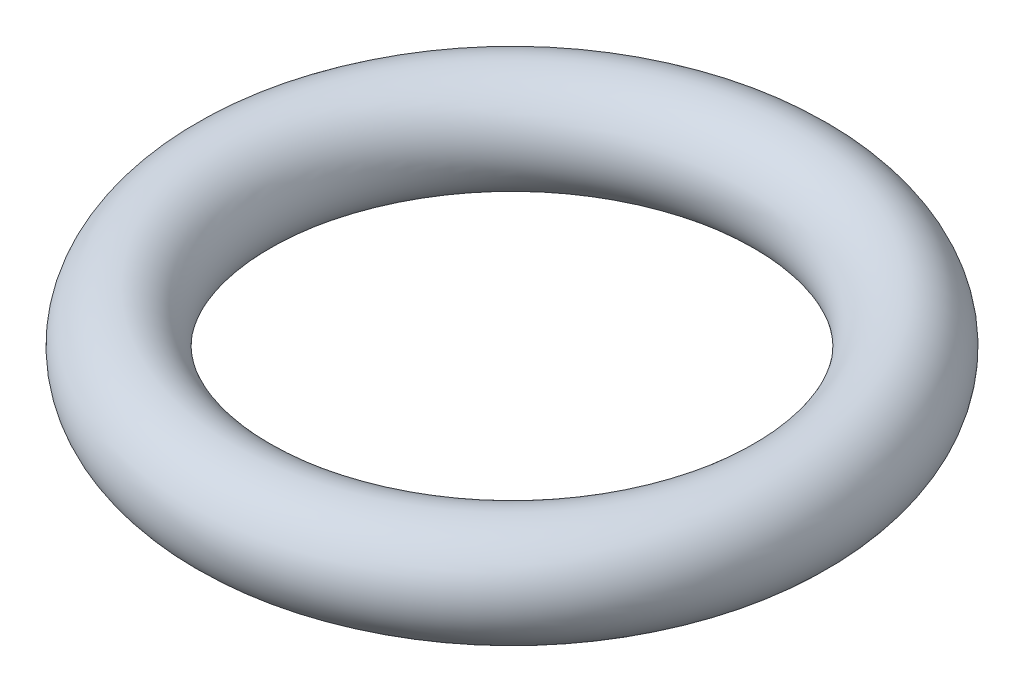
SolidWorks part; units mm, degrees
ref_plane "Front Plane" through (0, 0, 0) normal (0, 0, 1) x (1, 0, 0)
ref_plane "Top Plane" through (0, 0, 0) normal (0, 1, 0) x (1, 0, 0)
ref_plane "Right Plane" through (0, 0, 0) normal (1, 0, 0) x (0, 0, -1)
sketch "Sketch1" plane through (0, 0, 0) normal (0, 0, 1) x (1, 0, 0)
  line L0 (0, 0) -> (4.69, 0) construction
  line L1 (0, 0) -> (0, 8.2441) construction
  circle A0 centre (4.69, 0) radius 0.865
  dimension "D2" = 5.555
  dimension "D1" = 3.825
revolve "Revolve1" add sketch "Sketch1" angle 360 about L1
ref_axis "Axis1" through (0, 0, 0) along (0, 1, 0)
